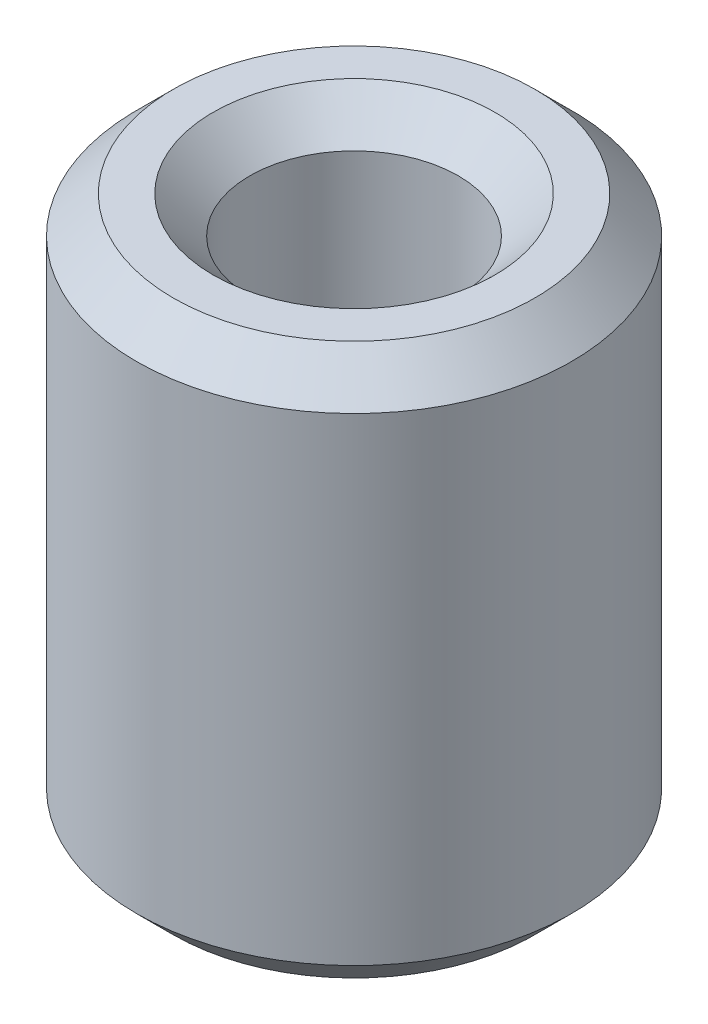
SolidWorks part; units mm, degrees
ref_plane "Front Plane" through (0, 0, 0) normal (0, 0, 1) x (1, 0, 0)
ref_plane "Top Plane" through (0, 0, 0) normal (0, 1, 0) x (1, 0, 0)
ref_plane "Right Plane" through (0, 0, 0) normal (1, 0, 0) x (0, 0, -1)
sketch "Sketch1" plane through (0, 0, 0) normal (0, 1, 0) x (1, 0, 0)
  circle A0 centre (0, 0) radius 7.5
  dimension "SLEEVE_OD" = 15
extrude "Boss-Extrude1" add sketch "Sketch1" along normal blind 19.0142
sketch "Sketch2" plane through (0, 0, 0) normal (0, 1, 0) x (1, 0, 0)
  circle A0 centre (0, 0) radius 3.5951
  dimension "BORE_D" = 7.1903
extrude "Cut-Extrude1" cut sketch "Sketch2" along normal through all
chamfer "Chamfer1" distance 1.2647 angle 45 4 edges at (0, 19.0142, 3.5951) (0, 0, 3.5951) (0, 0, 7.5) (0, 19.0142, 7.5)
